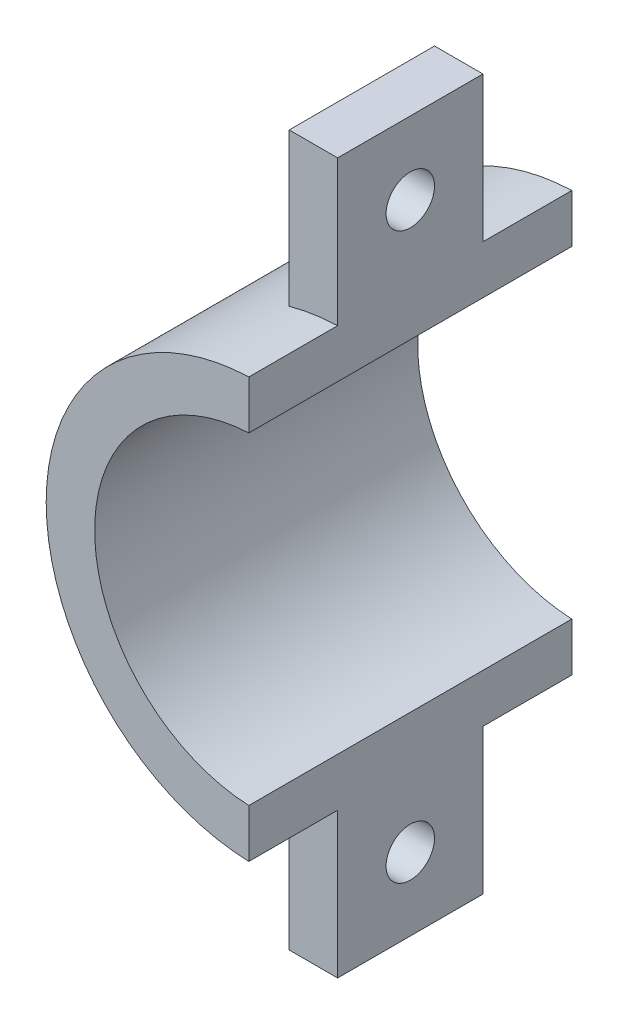
SolidWorks part; units mm, degrees
ref_plane "Спереди" through (0, 0, 0) normal (0, 0, 1) x (1, 0, 0)
ref_plane "Сверху" through (0, 0, 0) normal (0, 1, 0) x (1, 0, 0)
ref_plane "Справа" through (0, 0, 0) normal (1, 0, 0) x (0, 0, -1)
sketch "Эскиз1" plane through (0, 0, 0) normal (0, 0, 1) x (1, 0, 0)
  line L2 (0, 0) -> (0, 22.5479) construction
  line L3 (0, 0) -> (-0.4537, 12.9921) construction
  line L4 (0, 0) -> (-0.4537, -12.9921) construction
  line L5 (-0.4537, -12.9921) -> (-0.4537, 12.9921)
  circle A2 centre (0, 0) radius 10
  circle A3 centre (0, 0) radius 13
  dimension "D1" = 2
  dimension "D4" = 26
  dimension "D5" = 20
  dimension "D2" = 2
extrude "Бобышка-Вытянуть1" add sketch "Эскиз1" along normal blind 20 contours L5 A3 A2 region at (-12.7115, 0, 0)
sketch "Эскиз3" plane through (-0.4537, 0, 0) normal (1, 0, 0) x (0, 0, -1)
  line L0 (-10, 9.9897) -> (-10, -9.9897) construction
  line L1 (-14.5, 9.9897) -> (-5.5, 9.9897)
  line L4 (-14.5, 9.9897) -> (-14.5, 21.9897)
  line L5 (-14.5, 21.9897) -> (-5.5, 21.9897)
  line L6 (-5.5, 21.9897) -> (-5.5, 9.9897)
  line L8 (-20, 9.9897) -> (0, 9.9897) construction
  line L10 (-14.5, -9.9897) -> (-14.5, -21.9897)
  line L11 (-14.5, -21.9897) -> (-5.5, -21.9897)
  line L12 (-5.5, -21.9897) -> (-5.5, -9.9897)
  line L14 (-14.5, -9.9897) -> (-5.5, -9.9897)
  line L15 (-20, -9.9897) -> (0, -9.9897) construction
  circle A0 centre (-10, 17.4897) radius 1.5
  circle A1 centre (-10, -17.4897) radius 1.5
  point P4 (0, 0)
  point P5 (0, 0)
  point P18 (0, 0)
  point P21 (0, 0)
  point P22 (0, 0)
  dimension "D1" = 3
  dimension "D2" = 4.5
  dimension "D3" = 9
  dimension "D4" = 12
  dimension "D5" = 4.5
  dimension "D6" = 7.5
  dimension "D7" = 7.5
extrude "Бобышка-Вытянуть2" add sketch "Эскиз3" against normal blind 3
